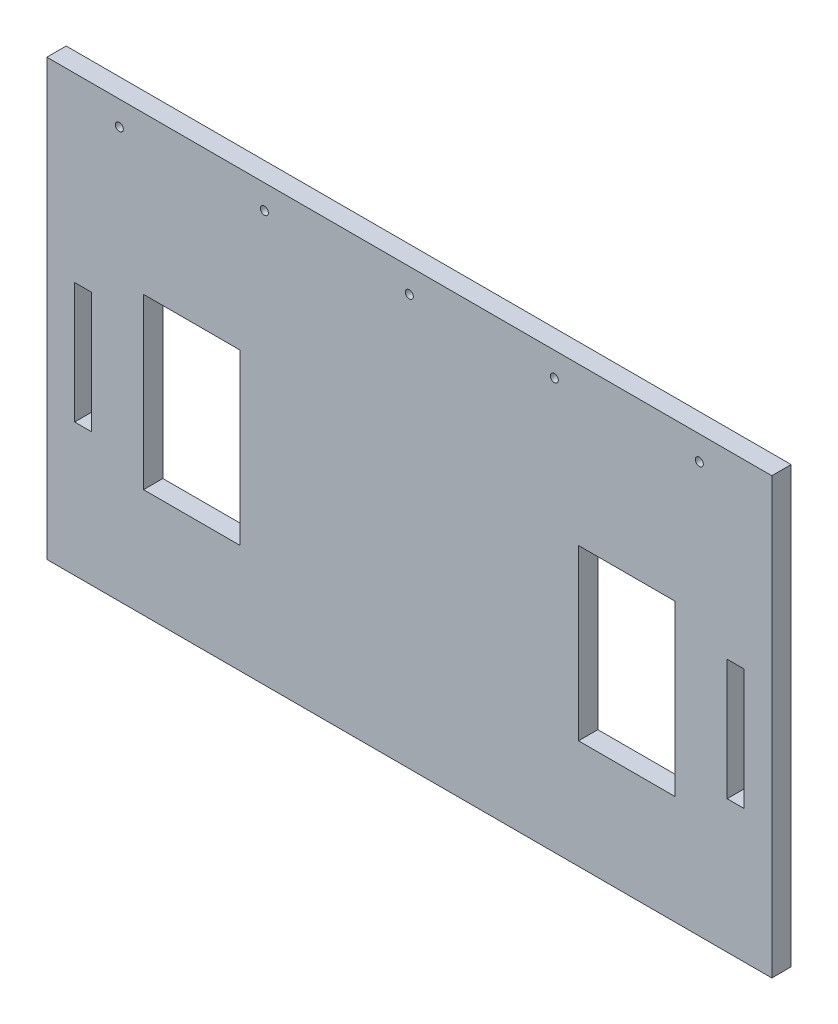
SolidWorks part; units mm, degrees
ref_plane "Front" through (0, 0, 0) normal (0, 0, 1) x (1, 0, 0)
ref_plane "Top" through (0, 0, 0) normal (0, 1, 0) x (1, 0, 0)
ref_plane "Right" through (0, 0, 0) normal (1, 0, 0) x (0, 0, -1)
sketch "Esquisse1" plane through (0, 0, 0) normal (0, 0, 1) x (1, 0, 0)
  line L1 (0, 0) -> (300, 0)
  line L2 (0, 0) -> (0, 180)
  line L3 (0, 180) -> (300, 180)
  line L4 (300, 0) -> (300, 180)
  dimension "D1" = 300
  dimension "D2" = 180
extrude "Boss.-Extru.1" add sketch "Esquisse1" along normal blind 8
sketch "Esquisse2" plane through (0, 0, 8) normal (0, 0, 1) x (1, 0, 0)
  line L0 (150, 180) -> (150, 0) construction
  line L1 (40, 45) -> (80, 45)
  line L2 (40, 45) -> (40, 115)
  line L3 (40, 115) -> (80, 115)
  line L4 (80, 45) -> (80, 115)
  line L5 (300, 180) -> (0, 180) construction
  line L6 (0, 0) -> (300, 0) construction
  line L7 (80, 80) -> (150, 80) construction
  line L8 (60, 45) -> (60, 115) construction
  line L9 (40, 80) -> (18.5, 80) construction
  line L10 (15, 55) -> (15, 105) construction
  line L11 (11.5, 55) -> (18.5, 55)
  line L12 (11.5, 55) -> (11.5, 105)
  line L13 (11.5, 105) -> (18.5, 105)
  line L14 (18.5, 55) -> (18.5, 105)
  line L15 (285, 55) -> (285, 105) construction
  line L16 (260, 80) -> (281.5, 80) construction
  line L17 (240, 45) -> (240, 115) construction
  line L18 (281.5, 55) -> (281.5, 105)
  line L19 (288.5, 105) -> (281.5, 105)
  line L20 (288.5, 55) -> (288.5, 105)
  line L21 (288.5, 55) -> (281.5, 55)
  line L22 (220, 45) -> (220, 115)
  line L23 (260, 115) -> (220, 115)
  line L24 (260, 45) -> (260, 115)
  line L25 (260, 45) -> (220, 45)
  dimension "D1" = 100
  dimension "D2" = 70
  dimension "D3" = 40
  dimension "D4" = 180
  dimension "D5" = 7
  dimension "D6" = 50
  dimension "D7" = 270
extrude "Enlèv. mat.-Extru.1" cut sketch "Esquisse2" against normal through all
sketch "Esquisse3" plane through (0, 0, 8) normal (0, 0, 1) x (1, 0, 0)
  line L0 (0, 170) -> (300, 170) construction
  line L1 (0, 180) -> (0, 0) construction
  line L2 (300, 0) -> (300, 180) construction
  line L3 (180, 160) -> (180, 172.6988) construction
  line L4 (300, 180) -> (0, 180) construction
  line L5 (150, 170) -> (150, 176.3559) construction
  circle A0 centre (270, 170) radius 1.65
  circle A1 centre (210, 170) radius 1.65
  circle A2 centre (150, 170) radius 1.65
  circle A3 centre (90, 170) radius 1.65
  circle A4 centre (30, 170) radius 1.65
  dimension "D1" = 3.3
  dimension "D2" = 60
  dimension "D3" = 60
  dimension "D5" = 60
  dimension "D4" = 10
extrude "Enlèv. mat.-Extru.2" cut sketch "Esquisse3" against normal up to vertex (8 mm away) up to point (300, 180, 0)
